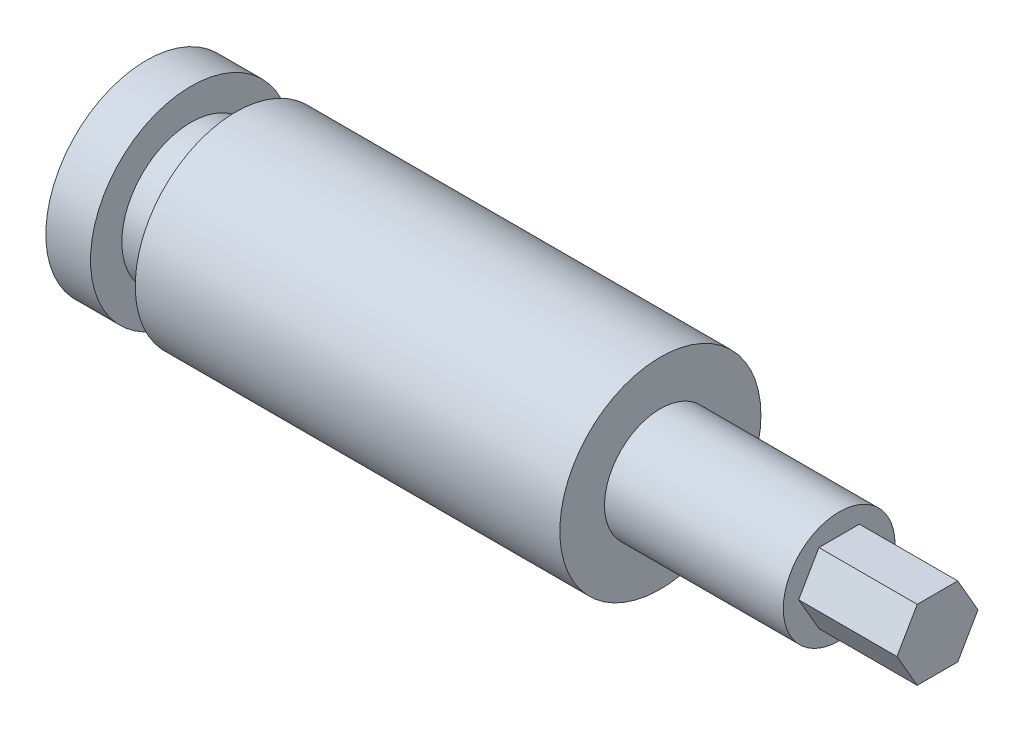
SolidWorks part; units mm, degrees
material "AISI 304"
ref_plane "Спереди" through (0, 0, 0) normal (0, 0, 1) x (1, 0, 0)
ref_plane "Сверху" through (0, 0, 0) normal (0, 1, 0) x (1, 0, 0)
ref_plane "Справа" through (0, 0, 0) normal (1, 0, 0) x (0, 0, -1)
ref_axis "Ось1" through (0, 0, 0) along (1, 0, 0)
sketch "Эскиз1" plane through (0, 0, 0) normal (0, 0, 1) x (1, 0, 0)
  line L0 (0, 0) -> (0, 4.5)
  line L1 (0, 4.5) -> (2, 4.5)
  line L2 (2, 4.5) -> (2, 3.1)
  line L3 (2, 3.1) -> (4, 3.1)
  line L4 (4, 3.1) -> (4, 4.5)
  line L5 (4, 4.5) -> (23, 4.5)
  line L6 (23, 4.5) -> (23, 2.5)
  line L7 (23, 2.5) -> (35.4, 2.5)
  line L8 (35.4, 2.5) -> (35.4, 0)
  line L9 (35.4, 0) -> (0, 0)
  line L10 (31, 2.5) -> (31, 1.57) construction
  line L11 (31, 1.57) -> (35.4, 1.57) construction
  line L12 (0, 0) -> (-8.3017, 0) construction
  point P15 (23, 3.5)
  dimension "D1" = 5
  dimension "D2" = 9
  dimension "D3" = 6.2
  dimension "D4" = 3.14
  dimension "D5" = 35.4
  dimension "D6" = 2
  dimension "D7" = 2
  dimension "D8" = 4.4
  dimension "D9" = 12.4
  dimension "D10" = 19
revolve "Повернуть1" add sketch "Эскиз1" angle 360 about L12
sketch "Эскиз2" plane through (0, 0, 0) normal (0, 0, 1) x (1, 0, 0)
  line L0 (31, 2.5) -> (31, 1.57) construction
  line L1 (31, 1.57) -> (35.4, 1.57) construction
  line L2 (35.4, 2.5) -> (35.4, 0) construction
  line L3 (23, 2.5) -> (35.4, 2.5) construction
  line L4 (31, 2.5) -> (31, 1.57)
  line L5 (31, 1.57) -> (35.4, 1.57)
  line L6 (35.4, 2.5) -> (35.4, 1.57)
  line L7 (31, 2.5) -> (35.4, 2.5)
extrude "Вырез-Вытянуть1" cut sketch "Эскиз2" against normal through all and the other way through all
pattern_circular "Круговой массив1" count 6 over 360 about axis through (0, 0, 0) along (1, 0, 0) of "Вырез-Вытянуть1"
hole_wizard "Отверстие обработанное метчиком M31" positions "Эскиз3" profile "Эскиз4" tap size "M3" standard "ISO"
sketch "Эскиз3" plane through (0, 0, 0) normal (-1, 0, 0) x (0, 0, 1)
  point P0 (0, 0)
sketch "Эскиз4" plane through (0, 0, 0) normal (0, 1, 0) x (0, 0, 1)
  line L0 (0, 0) -> (0, 9.2511)
  line L1 (0, 9.2511) -> (1.25, 8.5)
  line L2 (1.25, 8.5) -> (1.25, 0.35)
  line L3 (1.25, 0.35) -> (1.6, 0)
  line L5 (1.6, 0) -> (0, 0)
  line L6 (-1.25, 0.35) -> (-1.6, 0) construction
  line L10 (0, 9.2511) -> (-1.25, 8.5) construction
  line L11 (0, -6.35) -> (0, 107.95) construction
  dimension "Диаметр сверла" = 2.5
  dimension "Глубина сверла" = 8.5
  dimension "Диаметр передней зенковки" = 3.2
  dimension "Угол передней зенковки" = 90
  dimension "Угол заточки сверла" = 118
cosmetic thread "Отверстие резьбы1" parameters "D1"=6, "D2"=3
